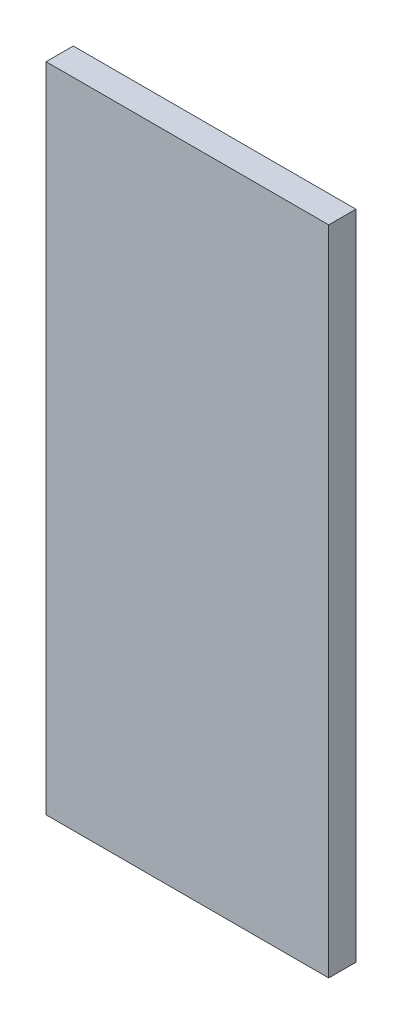
SolidWorks part; units mm, degrees
ref_plane "Front Plane" through (0, 0, 0) normal (0, 0, 1) x (1, 0, 0)
ref_plane "Top Plane" through (0, 0, 0) normal (0, 1, 0) x (1, 0, 0)
ref_plane "Right Plane" through (0, 0, 0) normal (1, 0, 0) x (0, 0, -1)
sketch "Sketch1" plane through (0, 0, 0) normal (0, 0, 1) x (1, 0, 0)
  line L0 (-1.8836, -40.741) -> (-1.8836, 111.659) construction
  line L1 (-34.9036, -40.741) -> (31.1364, -40.741)
  line L2 (-34.9036, -40.741) -> (-34.9036, 111.659)
  line L3 (-34.9036, 111.659) -> (31.1364, 111.659)
  line L4 (31.1364, -40.741) -> (31.1364, 111.659)
  line L5 (-34.9036, -40.741) -> (-34.9036, 111.659) construction
  line L6 (31.1364, 111.659) -> (31.1364, -40.741) construction
  dimension "D2" = 152.4
extrude "Boss-Extrude1" add sketch "Sketch1" along normal blind 6.35
